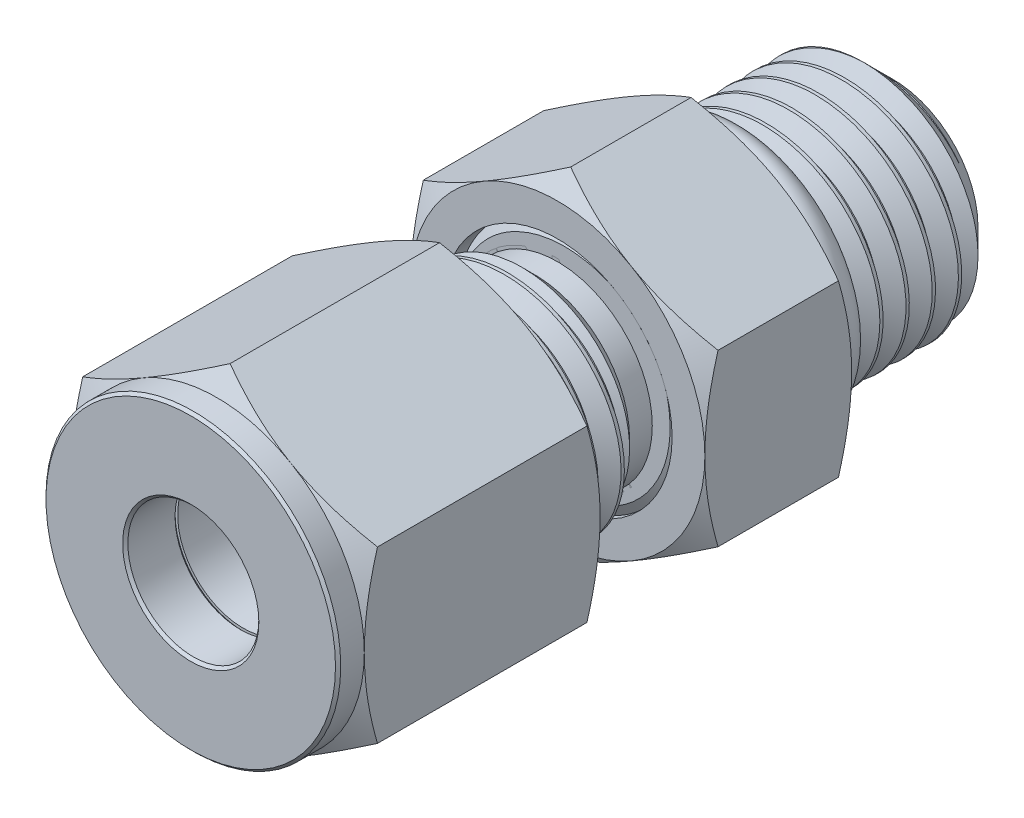
SolidWorks part; units mm, degrees
note: '?' marks a value the reader was unsure of.
ref_plane "Front Plane" through (0, 0, 0) normal (0, 0, 1) x (1, 0, 0)
ref_plane "Top Plane" through (0, 0, 0) normal (0, 1, 0) x (1, 0, 0)
ref_plane "Right Plane" through (0, 0, 0) normal (1, 0, 0) x (0, 0, -1)
sketch "Sketch1" plane through (0, 0, 0) normal (1, 0, 0) x (0, 0, -1)
  line L0 (0, 0) -> (34.036, 0) construction
  line L1 (0, 3.175) -> (0, -3.175) construction
  line L2 (12.7, 7.1437) -> (12.7, -7.1437) construction
  line L3 (5.08, 5.5562) -> (5.08, -5.5562) construction
  line L4 (5.08, 5.5562) -> (5.08, 4.2862) construction
  line L5 (24.892, 7.1437) -> (24.892, -7.1437) construction
  line L6 (4.445, 4.699) -> (9.3218, 3.6068) construction
  line L7 (9.3218, 3.6068) -> (9.3218, 3.175) construction
  line L8 (9.3218, 3.175) -> (5.1308, 3.175) construction
  line L9 (5.1308, 3.175) -> (4.445, 3.8608) construction
  line L10 (4.445, 3.8608) -> (4.445, 4.699) construction
  line L11 (2.54, 4.6609) -> (3.556, 4.6609) construction
  line L12 (3.556, 4.6609) -> (3.556, 3.8608) construction
  line L13 (3.556, 3.8608) -> (4.445, 3.8608) construction
  line L14 (24.892, 2.3749) -> (24.892, -2.3749) construction
  line L15 (4.445, 3.8608) -> (4.445, 3.175) construction
  line L16 (5.1308, 3.175) -> (2.54, 3.175) construction
  line L17 (2.54, 3.175) -> (2.54, 4.6609) construction
  line L18 (4.445, 3.175) -> (5.1308, 3.175) construction
  line L19 (0, 3.175) -> (2.54, 3.175) construction
  line L20 (2.54, 3.175) -> (5.08, 3.175) construction
  line L21 (34.036, 5.5562) -> (34.036, -5.5562) construction
  line L22 (24.892, 5.5562) -> (24.892, -5.5563) construction
  line L23 (24.892, 5.5562) -> (34.036, 5.5562) construction
  line L24 (24.892, 5.5562) -> (24.892, 4.2862) construction
  line L25 (25.8064, 6.2865) -> (25.8064, 4.4577) construction
  line L26 (34.036, 3.4163) -> (34.036, -3.4163) construction
  circle A0 centre (25.8064, 5.3721) radius 0.9144 construction
  point P4 (1.27, 0)
  point P10 (5.08, 0)
  point P12 (12.7, 0)
  point P15 (17.78, 0)
  point P16 (7.366, 0)
  point P17 (15.24, 0)
  point P40 (24.892, 0)
  dimension "R" = 9.144
sketch "Sketch2" plane through (0, 0, 0) normal (0, 0, 1) x (1, 0, 0)
  line L0 (0, 3.175) -> (0, -3.175) construction
  line L1 (0, 8.2489) -> (-7.1437, 4.1244)
  line L2 (-7.1437, 4.1244) -> (-7.1438, -4.1244)
  line L3 (-7.1438, -4.1244) -> (0, -8.2489)
  line L4 (0, -8.2489) -> (7.1437, -4.1244)
  line L5 (7.1437, -4.1244) -> (7.1438, 4.1244)
  line L6 (7.1438, 4.1244) -> (0, 8.2489)
  line L7 (0, 8.2489) -> (0, 0) construction
  circle A0 centre (0, 0) radius 7.1438 construction
extrude "Boss-Extrude1" add sketch "Sketch2" against normal up to vertex (12.7 mm away) up to point (0, 0, -12.7)
sketch "Sketch3" plane through (0, 0, 0) normal (1, 0, 0) x (0, 0, -1)
  line L0 (0, 8.2489) -> (0, 7.1437)
  line L1 (0, 4.1244) -> (0, 8.2489) construction
  line L2 (0, 7.1437) -> (1.27, 7.1437)
  line L3 (1.27, 7.1437) -> (1.9081, 8.2489)
  line L4 (12.7, 8.2489) -> (0, 8.2489) construction
  line L5 (1.9081, 8.2489) -> (12.0619, 8.2489)
  line L6 (12.0619, 8.2489) -> (12.7, 7.1437)
  line L7 (12.7, 7.1437) -> (12.7, 8.2489)
  line L8 (12.7, 8.2489) -> (12.7, 9.354)
  line L9 (12.7, 9.354) -> (0, 9.354)
  line L10 (0, 9.354) -> (0, 8.2489)
  line L11 (0, 3.175) -> (0, 0)
  line L12 (0, 3.175) -> (0, -3.175) construction
  line L13 (0, 0) -> (12.7, 0)
  line L14 (12.7, 7.1437) -> (12.7, -7.1437) construction
  line L15 (12.7, 0) -> (12.7, 5.5562)
  line L16 (12.7, 5.5562) -> (5.08, 5.5562)
  line L17 (5.08, 5.5562) -> (5.08, 4.2862) construction
  line L18 (5.08, 4.2862) -> (2.54, 4.2862) construction
  line L19 (2.54, 4.2862) -> (2.54, 3.175)
  line L20 (2.54, 3.175) -> (0, 3.175)
  line L21 (2.54, 4.2862) -> (2.54, 5.5562) construction
  line L22 (2.54, 5.5562) -> (5.08, 5.5562) construction
  line L23 (5.08, 4.9212) -> (2.54, 4.9212)
  line L24 (2.54, 4.9212) -> (2.54, 4.2862)
  line L25 (5.08, 4.9212) -> (5.08, 5.5562)
  dimension "D1" = 30
  dimension "D2" = 1.27
revolve "Cut-Revolve1" cut sketch "Sketch3" angle 360 about L0
chamfer "Chamfer1" distance 0.127 angle 45 3 edges at (3.175, 0, -2.54) (3.175, 0, 0) (7.1437, 0, 0)
sketch "Sketch4" plane through (0, 0, 0) normal (1, 0, 0) x (0, 0, -1)
  line L1 (24.892, 0) -> (7.366, 0)
  line L2 (24.892, 0) -> (24.892, 5.5563)
  line L3 (24.892, 5.5563) -> (7.366, 5.5562)
  line L4 (7.366, 0) -> (7.366, 5.5562)
  dimension "D1" = 17.526
revolve "Revolve1" add sketch "Sketch4" angle 360 about L1
sketch "Sketch7" plane through (0, 0, -24.892) normal (0, 0, -1) x (-1, 0, 0)
  line L0 (0, 0) -> (0, 8.2489) construction
  line L1 (0, 8.2489) -> (-7.1438, 4.1244)
  line L2 (-7.1438, 4.1244) -> (-7.1438, -4.1244)
  line L3 (-7.1438, -4.1244) -> (0, -8.2489)
  line L4 (0, -8.2489) -> (7.1437, -4.1244)
  line L5 (7.1437, -4.1244) -> (7.1438, 4.1244)
  line L6 (7.1438, 4.1244) -> (0, 8.2489)
  circle A0 centre (0, 0) radius 7.1438 construction
extrude "Boss-Extrude2" add sketch "Sketch7" against normal up to vertex (7.112 mm away) separate body up to point (0, 0, -17.78)
sketch "Sketch9" plane through (0, 0, 0) normal (1, 0, 0) x (0, 0, -1)
  line L0 (4.445, 4.699) -> (4.445, 3.8608)
  line L1 (4.445, 3.8608) -> (5.1308, 3.175)
  line L2 (5.1308, 3.175) -> (9.3218, 3.175)
  line L3 (9.3218, 3.175) -> (9.3218, 3.6068)
  line L4 (9.3218, 3.6068) -> (4.445, 4.699)
revolve "Revolve2" add sketch "Sketch9" angle 360 about L0
sketch "Sketch10" plane through (0, 0, 0) normal (1, 0, 0) x (0, 0, -1)
  line L0 (2.54, 4.6609) -> (3.556, 4.6609)
  line L1 (3.556, 4.6609) -> (3.556, 3.8608)
  line L2 (3.556, 3.8608) -> (4.445, 3.8608)
  line L4 (4.445, 3.8608) -> (5.1308, 3.175)
  line L5 (5.1308, 3.175) -> (2.54, 3.175)
  line L6 (2.54, 3.175) -> (2.54, 4.6609)
revolve "Revolve3" add sketch "Sketch10" angle 360 about L0
sketch "Sketch11" plane through (0, 0, 0) normal (1, 0, 0) x (0, 0, -1)
  line L0 (24.892, 0) -> (34.036, 0)
  line L1 (34.036, 0) -> (34.036, 5.5562)
  line L2 (34.036, 5.5562) -> (24.892, 5.5562)
  line L3 (24.892, 5.5562) -> (24.892, 0)
revolve "Revolve4" add sketch "Sketch11" angle 360 about L0
sketch "Sketch15" plane through (0, 0, 0) normal (1, 0, 0) x (0, 0, -1)
  line L0 (0, 0) -> (25.8064, 0) construction
  circle A0 centre (25.8064, 5.3721) radius 0.9144 construction
  circle A1 centre (25.8064, 5.3721) radius 0.9144
  point P3 (25.8064, 6.2865)
  point P7 (25.8064, -6.2865)
revolve "Revolve5" add sketch "Sketch15" angle 360 about L0
sketch "Sketch17" plane through (0, 0, -24.892) normal (0, 0, -1) x (-1, 0, 0)
  line L1 (7.1438, 4.1244) -> (0, 8.2489) construction
  line L2 (0, 8.2489) -> (-7.1438, 4.1244) construction
  line L3 (-7.1438, 4.1244) -> (-7.1438, -4.1244) construction
  line L4 (-7.1438, -4.1244) -> (0, -8.2489) construction
  line L5 (0, -8.2489) -> (7.1438, -4.1244) construction
  line L6 (7.1438, -4.1244) -> (7.1438, 4.1244) construction
  circle A0 centre (0, 0) radius 7.1438
extrude "Cut-Extrude1" cut sketch "Sketch17" against normal through all draft 60 flip side to cut
sketch "Sketch18" plane through (0, 0, -17.78) normal (0, 0, 1) x (1, 0, 0)
  circle A0 centre (0, 0) radius 7.1438 construction
  circle A1 centre (0, 0) radius 7.1438
extrude "Cut-Extrude2" cut sketch "Sketch18" against normal through all draft 60 flip side to cut
sketch "Sketch16" plane through (0, 0, 0) normal (1, 0, 0) x (0, 0, -1)
  line L0 (34.036, 0) -> (7.366, 0)
  line L1 (0, 0) -> (34.036, 0) construction
  line L2 (7.366, 0) -> (7.366, 4.0448)
  line L3 (4.445, 4.699) -> (9.3218, 3.6068) construction
  line L4 (7.366, 4.0448) -> (11.2498, 3.175)
  line L5 (11.2498, 3.175) -> (15.24, 3.175)
  line L6 (15.24, 3.175) -> (15.24, 2.3749)
  line L7 (15.24, 2.3749) -> (34.036, 2.3749)
  line L8 (34.036, 5.5562) -> (34.036, -5.5562) construction
  line L9 (34.036, 2.3749) -> (34.036, 0) construction
  line L10 (9.3218, 3.175) -> (5.1308, 3.175) construction
  line L11 (34.036, 2.3749) -> (35.6235, 2.3749)
  line L12 (35.6235, 2.3749) -> (35.6235, 0)
  line L13 (35.6235, 0) -> (34.036, 0)
  dimension "D1" = 1.5875
revolve "Cut-Revolve5" cut sketch "Sketch16" angle 360 about L0
combine bodies "Combine3" operation type add bodies to combine 106 115 114
chamfer "Chamfer2" distance 1.4287 angle 45 1 edges at (5.5562, 0, -34.036)
sketch "Sketch5" plane through (0, 0, -7.366) normal (0, 0, -1) x (-1, 0, 0)
  circle A0 centre (0, 0) radius 5.5562 construction
  circle A1 centre (0, 0) radius 5.5562
  point P3 (0, 5.5562)
curve "Helix/Spiral1" pitch 1.27 height 18.796 radius 5.5562 centre (0, 0, -7.366) axis (0, 0, -1) start towards (0, 1, 0)
sketch "Sketch6" plane through (0, 0, 0) normal (1, 0, 0) x (0, 0, -1)
  line L0 (6.1754, 5.6937) -> (7.4454, 5.6937) construction
  line L1 (7.4454, 5.6937) -> (6.8104, 4.5939) construction
  line L2 (6.8104, 4.5939) -> (6.1754, 5.6937) construction
  line L3 (6.731, 4.7314) -> (6.8898, 4.7314) construction
  line L4 (6.2547, 5.5562) -> (7.366, 5.5562) construction
  line L5 (6.8104, 4.5939) -> (6.8104, 4.7314) construction
  line L6 (6.8104, 5.5562) -> (6.8104, 5.6937) construction
  line L7 (6.731, 4.7314) -> (6.2151, 5.625)
  line L8 (6.2151, 5.625) -> (7.4057, 5.625)
  line L9 (7.4057, 5.625) -> (6.8898, 4.7314)
  line L10 (6.8898, 4.7314) -> (6.731, 4.7314)
  point P10 (6.8104, 5.625)
  dimension "D1" = 1.27
  dimension "D2" = 0.1588
sweep "Cut-Sweep1" cut profiles "Sketch6" path "Helix/Spiral1" align with end faces yes
sketch "Sketch8" plane through (0, 0, 0) normal (1, 0, 0) x (0, 0, -1)
  line L0 (7.366, 5.6937) -> (7.366, 4.5939)
  line L1 (7.366, 4.5939) -> (8.4659, 5.6937)
  line L2 (8.4659, 5.6937) -> (7.366, 5.6937)
  line L3 (17.78, 5.6937) -> (15.5803, 5.6937)
  line L4 (15.5803, 5.6937) -> (16.6801, 4.5939)
  line L5 (16.6801, 4.5939) -> (17.78, 4.5939)
  line L6 (17.78, 4.5939) -> (17.78, 5.6937)
  line L7 (17.78, 7.1437) -> (18.4181, 8.2489) construction
  line L8 (17.78, 8.2489) -> (17.78, 4.1244) construction
  line L9 (18.4181, 8.2489) -> (24.2539, 8.2489) construction
  line L10 (18.4181, 8.2489) -> (24.2539, 8.2489) construction
  line L11 (15.24, 2.3749) -> (24.892, 2.3749) construction
  line L12 (24.2539, 8.2489) -> (24.892, 7.1437) construction
  line L14 (24.892, 8.2489) -> (24.892, 9.354) construction
  line L15 (24.892, 9.354) -> (17.78, 9.354) construction
  line L16 (17.78, 9.354) -> (17.78, 8.2489) construction
  line L17 (17.78, 8.2489) -> (17.78, 7.1437) construction
  line L18 (6.8104, 4.5939) -> (7.366, 4.5939) construction
  line L19 (7.4454, 5.6937) -> (7.366, 5.6937) construction
  line L20 (8.4659, 5.6937) -> (15.5803, 5.6937) construction
  line L21 (16.6801, 4.5939) -> (7.366, 4.5939) construction
  line L22 (7.366, 4.0448) -> (11.2498, 3.175) construction
  line L23 (24.892, 7.1437) -> (24.892, 8.2489) construction
  line L24 (7.366, 3.9289) -> (7.366, -4.7433) construction
  line L25 (4.445, 4.699) -> (9.3218, 3.6068) construction
  line L26 (24.892, 0) -> (7.366, 0) construction
  line L27 (7.366, 0) -> (7.366, 4.0448) construction
  line L28 (11.2498, 3.175) -> (15.24, 3.175) construction
  line L29 (15.24, 3.175) -> (15.24, 2.3749) construction
  line L30 (24.892, 2.3749) -> (24.892, 0) construction
  line L31 (15.24, 0) -> (15.24, 2.3749) construction
  dimension "D1" = 30
revolve "Cut-Revolve2" cut sketch "Sketch8" angle 360 about L0
ref_plane "Plane2" through (0, 0, -35.306) normal (0, 0, -1) x (-1, 0, 0)
sketch "Sketch12" plane through (0, 0, -35.306) normal (0, 0, -1) x (-1, 0, 0)
  circle A0 centre (0, 0) radius 5.5562 construction
  circle A1 centre (0, 0) radius 4.1275
  circle A2 centre (0, 0) radius 4.1275
  point P0 (0, 5.5562)
  dimension "D1" = 0
curve "Helix/Spiral2" pitch 1.27 height 10.414 turns 8.2
sketch "Sketch13" plane through (0, 0, 0) normal (1, 0, 0) x (0, 0, -1)
  line L0 (35.2266, 5.6937) -> (36.4966, 5.6937) construction
  line L1 (35.2266, 5.6937) -> (35.8616, 4.5939) construction
  line L2 (35.8616, 4.5939) -> (36.4966, 5.6937) construction
  line L3 (35.7823, 4.7314) -> (35.941, 4.7314) construction
  line L4 (35.306, 5.5562) -> (36.4173, 5.5562) construction
  line L5 (35.8616, 4.5939) -> (35.8616, 4.7314) construction
  line L6 (35.8616, 5.5562) -> (35.8616, 5.6937) construction
  line L7 (35.8616, 5.625) -> (36.4569, 5.625) construction
  line L8 (35.8616, 4.5939) -> (35.8616, -5.5562) construction
  line L9 (35.8616, -5.5562) -> (34.5916, -5.5562) construction
  line L10 (34.5916, -5.5562) -> (33.3216, -5.5562) construction
  line L11 (33.3216, -5.5562) -> (32.0516, -5.5562) construction
  line L12 (35.2266, 5.6937) -> (36.4569, 5.625)
  line L13 (36.4569, 5.625) -> (35.941, 4.7314)
  line L14 (35.941, 4.7314) -> (35.7823, 4.7314)
  line L15 (35.7823, 4.7314) -> (35.2266, 5.6937)
  line L16 (24.892, -5.5562) -> (32.6073, -5.5562) construction
  line L17 (32.0516, -5.5562) -> (30.7816, -5.5563) construction
  line L18 (30.7816, -5.5563) -> (29.5116, -5.5562) construction
  dimension "D1" = 1.27
  dimension "D2" = 0.1588
sweep "Cut-Sweep2" cut profiles "Sketch13" path "Helix/Spiral2"
ref_plane "Plane1" through (-5.2843, 1.717, -26.0029) normal (-0.3088, -0.9504, 0.0372) x (0.9442, -0.3016, 0.1326)
sketch "Sketch14" plane through (0, 0, 0) normal (1, 0, 0) x (0, 0, -1)
  line L0 (35.8616, 4.5939) -> (34.036, 4.5939) construction
  line L1 (27.0917, 5.6937) -> (24.892, 5.6937)
  line L2 (34.036, 0) -> (24.892, 0) construction
  line L3 (34.036, 0) -> (34.036, 2.3749) construction
  line L4 (34.036, 2.3749) -> (24.892, 2.3749) construction
  line L5 (34.036, 5.5562) -> (34.036, -5.5562) construction
  line L6 (34.036, 4.5939) -> (32.9361, 5.6937) construction
  line L7 (32.9361, 5.6937) -> (34.036, 5.6937) construction
  line L8 (34.036, 5.6937) -> (34.036, 4.5939) construction
  line L9 (35.2266, 5.6937) -> (36.4966, 5.6937) construction
  line L10 (24.892, 0) -> (24.892, 2.3749) construction
  line L11 (24.892, 5.6937) -> (24.892, 4.5939)
  line L12 (24.892, 4.5939) -> (25.9919, 4.5939)
  line L13 (25.9919, 4.5939) -> (27.0917, 5.6937)
  line L14 (27.0917, 5.6937) -> (32.9361, 5.6937) construction
  line L15 (34.036, 4.5939) -> (25.9919, 4.5939) construction
  line L17 (24.892, 7.1437) -> (24.892, -7.1437) construction
revolve "Cut-Revolve4" cut sketch "Sketch14" angle 360 about L0
sketch "Sketch19" plane through (0, 0, 0) normal (1, 0, 0) x (0, 0, -1)
  line L5 (17.78, 6.1867) -> (17.78, 0) construction
  line L8 (17.78, 5.5562) -> (24.892, 5.5563)
  line L9 (17.78, 5.5562) -> (17.78, 4.7314)
  line L10 (17.78, 4.7314) -> (24.892, 4.7314)
  line L11 (24.892, 5.5563) -> (24.892, 4.7314)
  line L12 (24.892, 7.1437) -> (24.892, -7.1437) construction
revolve "Cut-Revolve7" cut sketch "Sketch19" angle 360 about L0
ref_axis "Center Axis 1" through (0, 0, -24.892) along (0, 0, -1)?
ref_plane "Contact Plane 1" through (0, 0, 0) normal (0, 0, 1) x (1, 0, 0)
ref_plane "Contact Plane 2" through (0, 0, -34.036) normal (0, 0, -1) x (-1, 0, 0)
equation "\"D4@Helix/Spiral1\" = \"Straight Thread Pitch@Sketch1\""
equation "\"D3@Helix/Spiral1\" = \"D4@Helix/Spiral1\" + \"D1@Sketch4\""
equation "\"D1@Sketch6\" = \"D4@Helix/Spiral1\""
equation "\"D2@Sketch6\" = \"D1@Sketch6\" / 8"
equation "\"D4@Helix/Spiral2\" = \"Thread Pitch@Sketch1\""
equation "\"D3@Helix/Spiral2\" = \"D4@Helix/Spiral2\" + \"R@Sketch1\""
equation "\"D1@Sketch13\" = \"D4@Helix/Spiral2\""
equation "\"D2@Sketch13\" = \"D1@Sketch13\" / 8"
